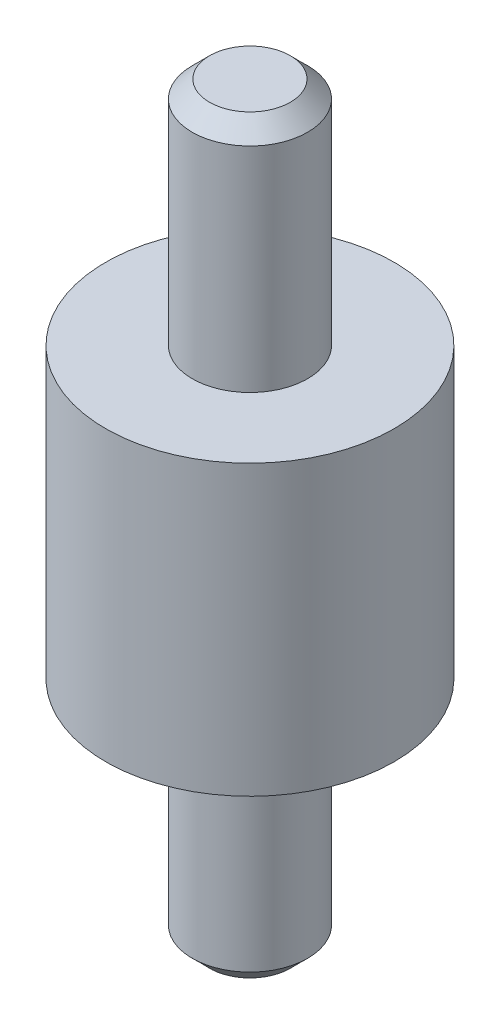
SolidWorks part; units mm, degrees
ref_plane "Front" through (0, 0, 0) normal (0, 0, 1) x (1, 0, 0)
ref_plane "Top" through (0, 0, 0) normal (0, 1, 0) x (1, 0, 0)
ref_plane "Right" through (0, 0, 0) normal (1, 0, 0) x (0, 0, -1)
sketch "Sketch1" plane through (0, 0, 0) normal (0, 0, 1) x (1, 0, 0)
  line L0 (0, 7.9375) -> (0, 20.6375)
  line L1 (-7.9375, -7.9375) -> (7.9375, -7.9375) construction
  line L2 (-7.9375, -7.9375) -> (-7.9375, 7.9375) construction
  line L3 (-7.9375, 7.9375) -> (7.9375, 7.9375) construction
  line L4 (7.9375, -7.9375) -> (7.9375, 7.9375) construction
  line L5 (-7.9375, -7.9375) -> (7.9375, 7.9375) construction
  line L6 (-7.9375, 7.9375) -> (7.9375, -7.9375) construction
  line L7 (0, 20.6375) -> (3.175, 20.6375)
  line L8 (3.175, 20.6375) -> (3.175, 7.9375)
  line L9 (-3.175, 7.9375) -> (-3.175, 20.6375) construction
  line L10 (-3.175, 20.6375) -> (3.175, 20.6375) construction
  line L11 (0, -7.9375) -> (0, -20.6375) construction
  line L12 (0, 7.9375) -> (3.175, 7.9375)
  line L13 (-3.175, -7.9375) -> (-3.175, -20.6375) construction
  line L14 (-3.175, -20.6375) -> (3.175, -20.6375) construction
  line L15 (3.175, -20.6375) -> (3.175, -7.9375) construction
  point P0 (0, 0)
revolve "Revolve1" add sketch "Sketch1" angle 360 mid plane about L0
sketch "Sketch3" plane through (0, 20.6375, 0) normal (0, 1, 0) x (1, 0, 0)
  circle A1 centre (0, 0) radius 3.175
  circle A2 centre (0, 0) radius 3.175
  dimension "D1" = 0
curve "Helix/Spiral1" [suppressed] pitch 1.27 height 13.97 turns 11 parameters "Thread Pitch"=1.27
sketch "Sketch2" plane through (0, 0, 0) normal (0, 0, 1) x (1, 0, 0)
  line L0 (3.175, 20.6375) -> (3.175, 21.7488) construction
  line L1 (3.175, 21.7488) -> (2.3501, 21.2725) construction
  line L2 (2.3501, 21.2725) -> (2.3501, 21.1138)
  line L3 (2.3501, 21.1138) -> (3.175, 20.6375) construction
  line L4 (2.3501, 21.1931) -> (3.175, 21.1931) construction
  line L5 (2.7626, 20.8756) -> (2.7626, 21.5106) construction
  line L6 (2.3501, 21.2725) -> (3.2004, 21.7634)
  line L7 (3.2004, 21.7634) -> (3.2004, 20.6228)
  line L8 (3.2004, 20.6228) -> (2.3501, 21.1138)
  dimension "D1" = 0.1588
  dimension "D2" = 0.635
  dimension "D3" = 0.0254
  dimension "D4" = 60
chamfer "Chamfer1" distance 0.9525 angle 45 1 edges at (0, 20.6375, -3.175)
sweep "Cut-Sweep1" [suppressed] cut profiles "Sketch2" path "Helix/Spiral1"
move or copy body "Body-Move/Copy1" bodies to move or copy 109 copy yes number of copies 1 rotation origin (0, 0, 0) rotation axis (1, 0, 0) rotation angle 180
sketch "Sketch4" plane through (0, 0, 0) normal (0, 0, 1) x (1, 0, 0)
  line L0 (0, -7.9375) -> (0, 7.9375)
  line L1 (-7.9375, -7.9375) -> (7.9375, -7.9375) construction
  line L2 (-7.9375, 7.9375) -> (7.9375, 7.9375) construction
  line L3 (0, 7.9375) -> (7.9375, 7.9375)
  line L4 (7.9375, 7.9375) -> (7.9375, -7.9375)
  line L5 (7.9375, -7.9375) -> (0, -7.9375)
revolve "Revolve2" add sketch "Sketch4" angle 360 mid plane about L0
equation "\"D1@Sketch2\" = \"Thread Pitch@Helix/Spiral1\" * .125"
equation "\"D2@Sketch2\" = \"Thread Pitch@Helix/Spiral1\" * .5"
equation "\"D1@Chamfer1\" = \"Thread Pitch@Helix/Spiral1\" * .75"
equation "\"D3@Helix/Spiral1\" = \"Thread Lg (C)@Sketch1\" + \"Thread Pitch@Helix/Spiral1\""
